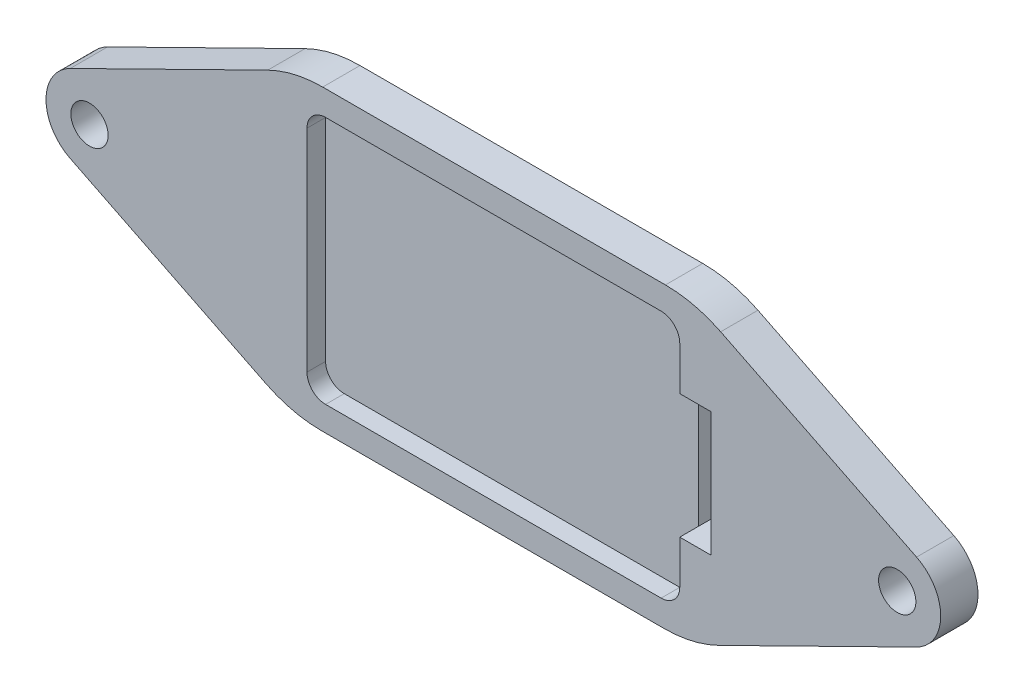
SolidWorks part; units mm, degrees
ref_plane "Front Plane" through (0, 0, 0) normal (0, 0, 1) x (1, 0, 0)
ref_plane "Top Plane" through (0, 0, 0) normal (0, 1, 0) x (1, 0, 0)
ref_plane "Right Plane" through (0, 0, 0) normal (1, 0, 0) x (0, 0, -1)
sketch "Sketch1" plane through (0, 0, 0) normal (0, 0, 1) x (1, 0, 0)
  line L0 (0, 20.0933) -> (0, -16.1178) construction
  line L1 (0, 0) -> (44.9398, 0) construction
  line L2 (-34.0467, 3.1397) -> (-18.1511, 10.9705)
  line L3 (-13.5, -10) -> (13.5, -10)
  line L4 (-15, -8.5) -> (-15, 8.5)
  line L5 (-13.5, 10) -> (13.5, 10)
  line L6 (15, -8.5) -> (15, 8.5)
  line L7 (-15, -10) -> (15, 10) construction
  line L8 (-15, 10) -> (15, -10) construction
  line L9 (-13.8471, -12) -> (13.7319, -12)
  line L11 (-13.7319, 12) -> (13.8471, 12)
  line L13 (-16.1919, -12) -> (16.1919, 12) construction
  line L14 (-16.0614, 12) -> (16.0614, -12) construction
  line L15 (-34.0558, -3.1352) -> (-18.2922, -10.9577)
  line L16 (18.1511, -10.9705) -> (34.0467, -3.1397)
  line L17 (18.2922, 10.9577) -> (34.0558, 3.1352)
  line L19 (17.5, -5) -> (15, -5)
  line L20 (17.5, -5) -> (17.5, 5)
  line L21 (17.5, 5) -> (15, 5)
  line L22 (15, -5) -> (15, 5)
  line L23 (17.5, -5) -> (15, 5) construction
  line L24 (17.5, 5) -> (15, -5) construction
  circle A0 centre (-32.5, 0) radius 1.5
  arc A1 (-34.0467, 3.1397) -> (-34.0558, -3.1352) centre (-32.5, 0) ccw
  circle A2 centre (32.5, 0) radius 1.5
  arc A3 (34.0467, -3.1397) -> (34.0558, 3.1352) centre (32.5, 0) ccw
  arc A4 (-13.8471, -12) -> (-18.2922, -10.9577) centre (-13.8471, -2) cw
  arc A5 (18.1511, -10.9705) -> (13.7319, -12) centre (13.7319, -2) cw
  arc A6 (18.2922, 10.9577) -> (13.8471, 12) centre (13.8471, 2) ccw
  arc A7 (-13.7319, 12) -> (-18.1511, 10.9705) centre (-13.7319, 2) ccw
  arc A8 (-13.5, -10) -> (-15, -8.5) centre (-13.5, -8.5) cw
  arc A9 (15, -8.5) -> (13.5, -10) centre (13.5, -8.5) cw
  arc A10 (15, 8.5) -> (13.5, 10) centre (13.5, 8.5) ccw
  arc A11 (-13.5, 10) -> (-15, 8.5) centre (-13.5, 8.5) ccw
  point P50 (16.25, 0)
  dimension "D1" = 3
  dimension "D2" = 7
  dimension "D4" = 10
  dimension "D8" = 1.5
  dimension "D3" = 32.5
  dimension "D5" = 20
  dimension "D6" = 2
  dimension "D7" = 30
  dimension "D9" = 10
  dimension "D10" = 2.5
extrude "Boss-Extrude1" add sketch "Sketch1" along normal blind 3 contours L11 A7 L2 A1 L15 A4 L9 A5 L16 A3 L17 A6 A11 L5 A10 L6 L21 L20 L19 A9 L3 A8 L4 A0 A2 region at (-25.7635, 6.3743, 0)
extrude "Boss-Extrude2" add sketch "Sketch1<3>" along normal blind 1.5 contours L5 A11 L4 A8 L3 A9 L6 A10 region at (0, 0, 0)
sketch "Sketch1<3>" plane through (0, 0, 0) normal (0, 0, 1) x (1, 0, 0) same geometry as "Sketch1"
